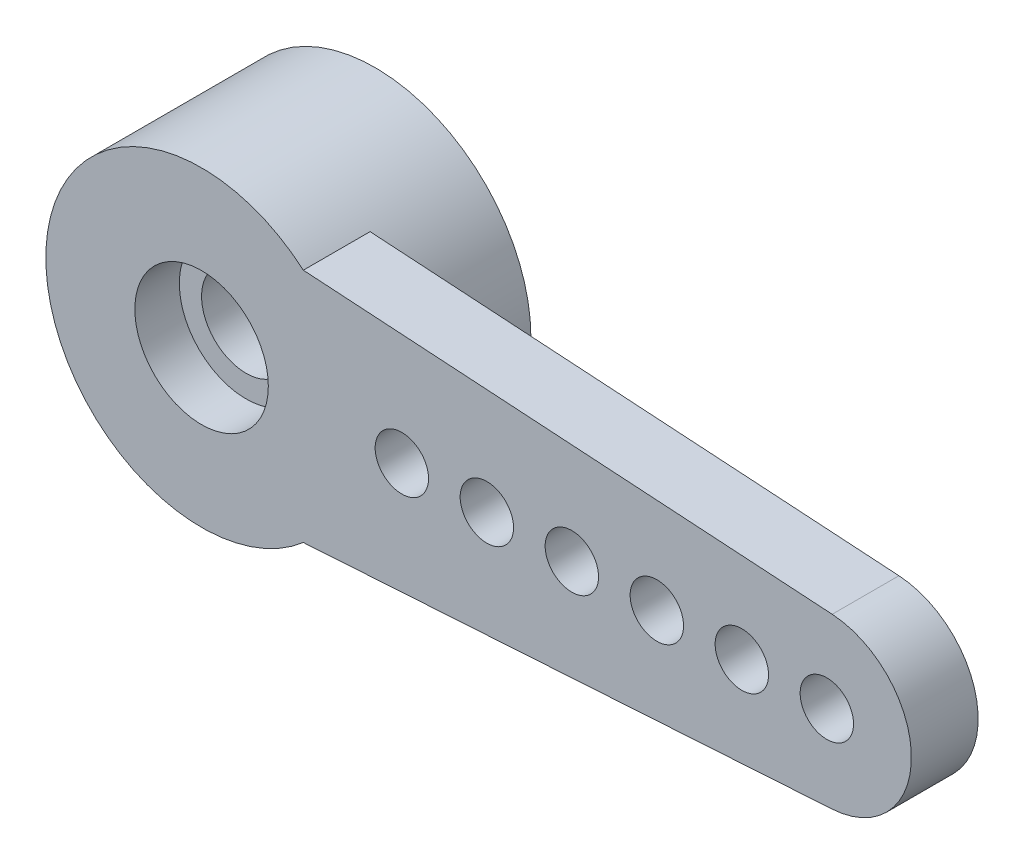
SolidWorks part; units mm, degrees
ref_plane "前视基准面" through (0, 0, 0) normal (0, 0, 1) x (1, 0, 0)
ref_plane "上视基准面" through (0, 0, 0) normal (0, 1, 0) x (1, 0, 0)
ref_plane "右视基准面" through (0, 0, 0) normal (1, 0, 0) x (0, 0, -1)
other "Configuration Table"
sketch "草图1" plane through (0, 0, 0) normal (0, 0, 1) x (1, 0, 0)
  line L12 (15.95, 15.99) -> (15.95, -15.1175) construction
  line L13 (0, 0) -> (14.05, 0) construction
  line L14 (2.2864, 2.65) -> (14.1703, 1.8962)
  line L15 (14.1703, -1.8962) -> (2.2864, -2.65)
  line L16 (2.2864, 2.65) -> (2.2864, -2.65)
  line L17 (4.5, 0) -> (6.41, 0)
  line L18 (6.41, 0) -> (8.32, 0)
  line L19 (8.32, 0) -> (10.23, 0)
  line L20 (10.23, 0) -> (12.14, 0)
  line L21 (12.14, 0) -> (14.05, 0)
  line L22 (-3.5, 5.9995) -> (-3.5, -4.0704) construction
  line L23 (4.5, 6.4068) -> (4.5, 4.4679) construction
  circle A0 centre (0, 0) radius 3.5
  circle A1 centre (0, 0) radius 1.5
  circle A2 centre (0, 0) radius 1
  circle A3 centre (0, 0) radius 2.5
  circle A4 centre (14.05, 0) radius 1.9
  circle A5 centre (14.05, 0) radius 0.6
  circle A6 centre (4.5, 0) radius 0.6
  circle A7 centre (6.41, 0) radius 0.6
  circle A8 centre (8.32, 0) radius 0.6
  circle A9 centre (10.23, 0) radius 0.6
  circle A10 centre (12.14, 0) radius 0.6
  dimension "D1" = 7
  dimension "D2" = 5
  dimension "D3" = 2
  dimension "D4" = 3
  dimension "D6" = 3.8
  dimension "D8" = 1.2
  dimension "D5" = 15.95
  dimension "D7" = 5.3
  dimension "D9" = 8
  dimension "D10" = 1.91
extrude "凸台-拉伸1" add sketch "草图1" along normal blind 3.9 contours A0
extrude "凸台-拉伸2" add sketch "草图1<6>" against normal blind 1.5 from surface contours A10 A4 L14 A0 L15 A9 A8 A7 A6 | A10 A5 A4 region at (8.2201, 2.1432, 0) region at (15.3967, 1.264, 0) starting at face at (3.5, 0, 3.9)
sketch "草图1<6>" plane through (0, 0, 0) normal (0, 0, 1) x (1, 0, 0) same geometry as "草图1"
extrude "切除-拉伸1" cut sketch "草图1<3>" along normal blind 2 contours A3
sketch "草图1<3>" plane through (0, 0, 0) normal (0, 0, 1) x (1, 0, 0) same geometry as "草图1"
extrude "切除-拉伸2" cut sketch "草图1<4>" against normal blind 1 from surface contours A1 starting at face at (7.2267, 0, 3.9)
sketch "草图1<4>" plane through (0, 0, 0) normal (0, 0, 1) x (1, 0, 0) same geometry as "草图1"
extrude "切除-拉伸3" cut sketch "草图1<5>" along normal through all contours A2
sketch "草图1<5>" plane through (0, 0, 0) normal (0, 0, 1) x (1, 0, 0) same geometry as "草图1"
